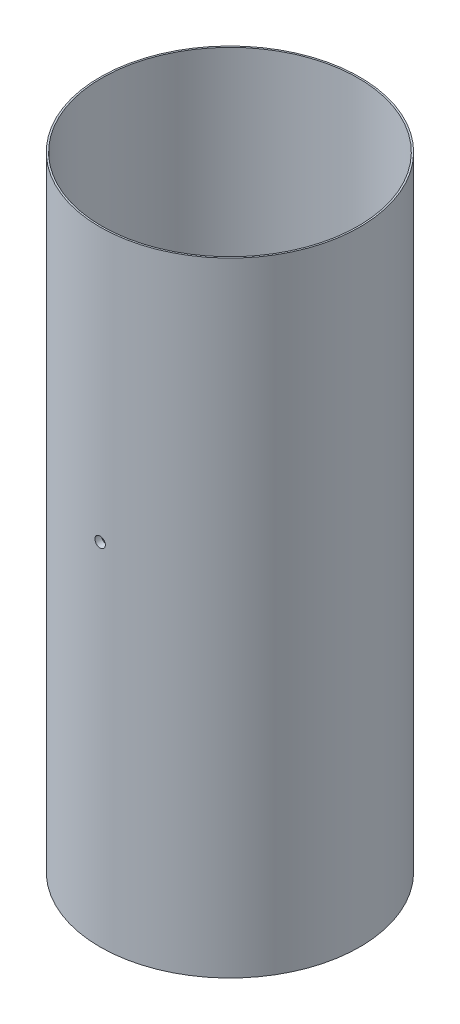
SolidWorks part; units mm, degrees
material "6061-T4 (SS)"
ref_plane "Front Plane" through (0, 0, 0) normal (0, 0, 1) x (1, 0, 0)
ref_plane "Top Plane" through (0, 0, 0) normal (0, 1, 0) x (1, 0, 0)
ref_plane "Right Plane" through (0, 0, 0) normal (1, 0, 0) x (0, 0, -1)
sketch "Sketch1" plane through (0, 0, 0) normal (0, 1, 0) x (1, 0, 0)
  circle A0 centre (0, 0) radius 63.5
  circle A1 centre (0, 0) radius 60.325
  dimension "D1" = 127
  dimension "D2" = 120.65
extrude "Boss-Extrude1" add sketch "Sketch1" along normal blind 304.8
sketch "Sketch5" plane through (0, 0, 0) normal (0, 1, 0) x (1, 0, 0)
  circle A0 centre (0, 0) radius 60.325
  circle A1 centre (0, 0) radius 62.7063
  dimension "D1" = 120.65
  dimension "D2" = 125.4125
extrude "Cut-Extrude1" cut sketch "Sketch5" along normal blind 158.75
sketch "Sketch6" plane through (0, 304.8, 0) normal (0, 1, 0) x (1, 0, 0)
  circle A0 centre (0, 0) radius 60.325
  circle A1 centre (0, 0) radius 62.7063
  dimension "D1" = 120.65
  dimension "D2" = 125.4125
extrude "Cut-Extrude2" cut sketch "Sketch6" against normal blind 120.65
ref_plane "Plane1" through (0, 0, 63.5) normal (0, 0, 1) x (1, 0, 0)
ref_plane "Plane2" through (0, 0, -63.5) normal (0, 0, 1) x (1, 0, 0)
sketch "Sketch8" plane through (0, 0, 63.5) normal (0, 0, 1) x (1, 0, 0)
  circle A0 centre (0, 171.45) radius 6.4556
  dimension "D1" = 171.45
sketch "Sketch12" plane through (0, 0, -63.5) normal (0, 0, 1) x (1, 0, 0)
  circle A0 centre (0, 171.45) radius 6.4556
hole_wizard "Tap Drill for 1/4-20 Tap8" positions "Sketch20" profile "Sketch19" hole size "1/4-20" standard "ANSI Inch" end condition up to next
sketch "Sketch20" plane through (0, 0, 63.5) normal (0, 0, 1) x (1, 0, 0)
  point P0 (0, 171.45)
sketch "Sketch19" plane through (0, 171.45, 63.5) normal (1, 0, 0) x (0, -1, 0)
  line L0 (0, 0) -> (0, 3.175)
  line L1 (0, 3.175) -> (2.5527, 3.175)
  line L2 (2.5527, 3.175) -> (2.5527, 0)
  line L5 (2.5527, 0) -> (0, 0)
  line L11 (0, -6.35) -> (0, 107.95) construction
  dimension "Thru Hole Dia." = 5.1054
  dimension "Thru Hole Depth" = 3.175
hole_wizard "Tap Drill for 1/4-20 Tap9" positions "Sketch21" profile "Sketch22" hole size "1/4-20" standard "ANSI Inch" end condition up to next
sketch "Sketch21" plane through (0, 0, -63.5) normal (0, 0, 1) x (1, 0, 0)
  point P0 (0, 171.45)
sketch "Sketch22" plane through (0, 171.45, -63.5) normal (1, 0, 0) x (0, 1, 0)
  line L0 (0, 0) -> (0, 3.175)
  line L1 (0, 3.175) -> (2.5527, 3.175)
  line L2 (2.5527, 3.175) -> (2.5527, 0)
  line L5 (2.5527, 0) -> (0, 0)
  line L11 (0, -6.35) -> (0, 107.95) construction
  dimension "Thru Hole Dia." = 5.1054
  dimension "Thru Hole Depth" = 3.175
